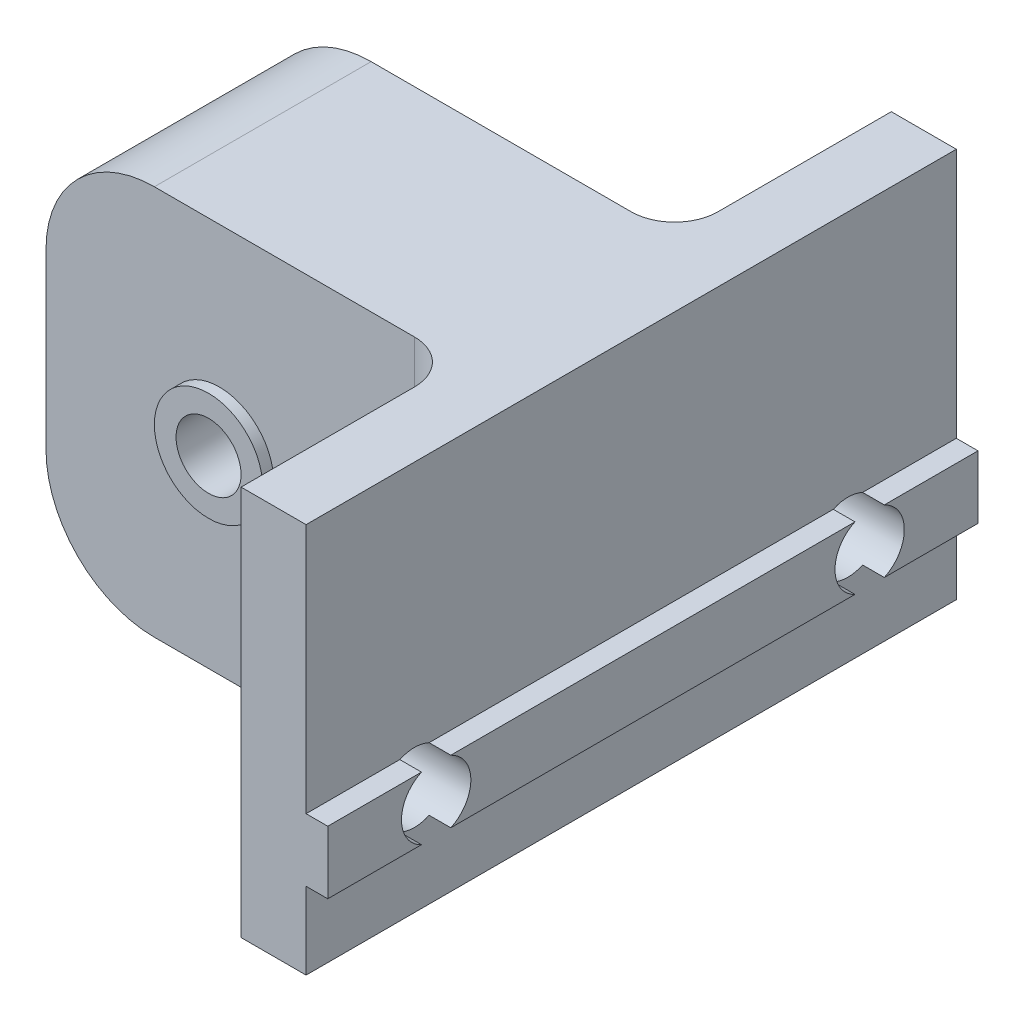
SolidWorks part; units mm, degrees
ref_plane "Front Plane" through (0, 0, 0) normal (0, 0, 1) x (1, 0, 0)
ref_plane "Top Plane" through (0, 0, 0) normal (0, 1, 0) x (1, 0, 0)
ref_plane "Right Plane" through (0, 0, 0) normal (1, 0, 0) x (0, 0, -1)
sketch "Esquisse1" plane through (0, 0, 0) normal (0, 0, 1) x (1, 0, 0)
  line L0 (-11, 13) -> (-11, -5)
  line L1 (-11, 13) -> (11, 13)
  line L2 (11, 13) -> (11, 1.45)
  line L3 (11, 1.45) -> (12, 1.45)
  line L4 (12, 1.45) -> (12, -1.45)
  line L5 (12, -1.45) -> (11, -1.45)
  line L6 (11, -1.45) -> (11, -5)
  line L7 (11, -5) -> (-11, -5)
  point P8 (12, 0)
  point P10 (0, -5)
  dimension "D1" = 2.9
  dimension "D2" = 18
  dimension "D3" = 1
  dimension "D4" = 22
  dimension "D5" = 3.55
extrude "Main Extrusion" add sketch "Esquisse1" along normal blind 30
sketch "Esquisse2" plane through (0, 13, 0) normal (0, 1, 0) x (1, 0, 0)
  line L0 (-11, -30) -> (-11, 0) construction
  line L1 (-11, 0) -> (8, 0)
  line L2 (-11, 0) -> (-11, -10)
  line L3 (-11, -10) -> (8, -10)
  line L4 (8, 0) -> (8, -10)
  line L5 (11, -30) -> (-11, -30) construction
  line L6 (-11, -30) -> (8, -30)
  line L7 (-11, -30) -> (-11, -20)
  line L8 (-11, -20) -> (8, -20)
  line L9 (8, -30) -> (8, -20)
  line L10 (11, 0) -> (-11, 0) construction
  line L12 (11, -30) -> (11, 0) construction
  dimension "D1" = 3
  dimension "D2" = 10
extrude "External Hole" cut sketch "Esquisse2" against normal through all
sketch "Esquisse3" plane through (8, 0, 0) normal (-1, 0, 0) x (0, 0, 1)
  line L1 (30, -5) -> (30, 13) construction
  line L4 (0, -1.45) -> (0, 1.45) construction
  line L5 (30, 1.45) -> (30, 13) construction
  circle A0 centre (5, 0) radius 1.6
  circle A1 centre (25, 0) radius 1.6
  point P5 (0, 0)
  point P10 (30, 4)
  point P12 (0, 0)
  point P13 (0, 0)
  point P14 (0, 0)
  point P15 (0, 0)
  dimension "D1" = 3.2
  dimension "D2" = 5
  dimension "D3" = 5
extrude "MakerBeamFixingHole" cut sketch "Esquisse3" against normal through all
sketch "Esquisse4" plane through (0, 0, 20) normal (0, 0, 1) x (1, 0, 0)
  line L0 (8, -5) -> (8, 13) construction
  line L1 (-11, -5) -> (-11, 13) construction
  circle A0 centre (-3, 4) radius 1.5
  point P7 (-11, 4)
  dimension "D1" = 3
  dimension "D2" = 11
extrude "HoleLinkWithCodersSupport" cut sketch "Esquisse4" against normal through all
fillet "Congé2" radius 2 2 edges at (8, 4, 20) (8, 4, 10)
fillet "Congé3" radius 5 2 edges at (-11, -5, 15) (-11, 13, 15)
sketch "Esquisse6" plane through (0, 0, 10) normal (0, 0, -1) x (-1, 0, 0)
  circle A0 centre (3, 4) radius 1.5
  circle A1 centre (3, 4) radius 1.5 construction
  circle A2 centre (3, 4) radius 2.5
  dimension "D1" = 5
extrude "Boss.-Extru.1" add sketch "Esquisse6" along normal blind 0.5
sketch "Esquisse7" plane through (0, 0, 20) normal (0, 0, 1) x (1, 0, 0)
  circle A0 centre (-3, 4) radius 1.5
  circle A1 centre (-3, 4) radius 1.5 construction
  circle A2 centre (-3, 4) radius 2.5
  dimension "D1" = 5
extrude "Boss.-Extru.2" add sketch "Esquisse7" along normal blind 0.5
